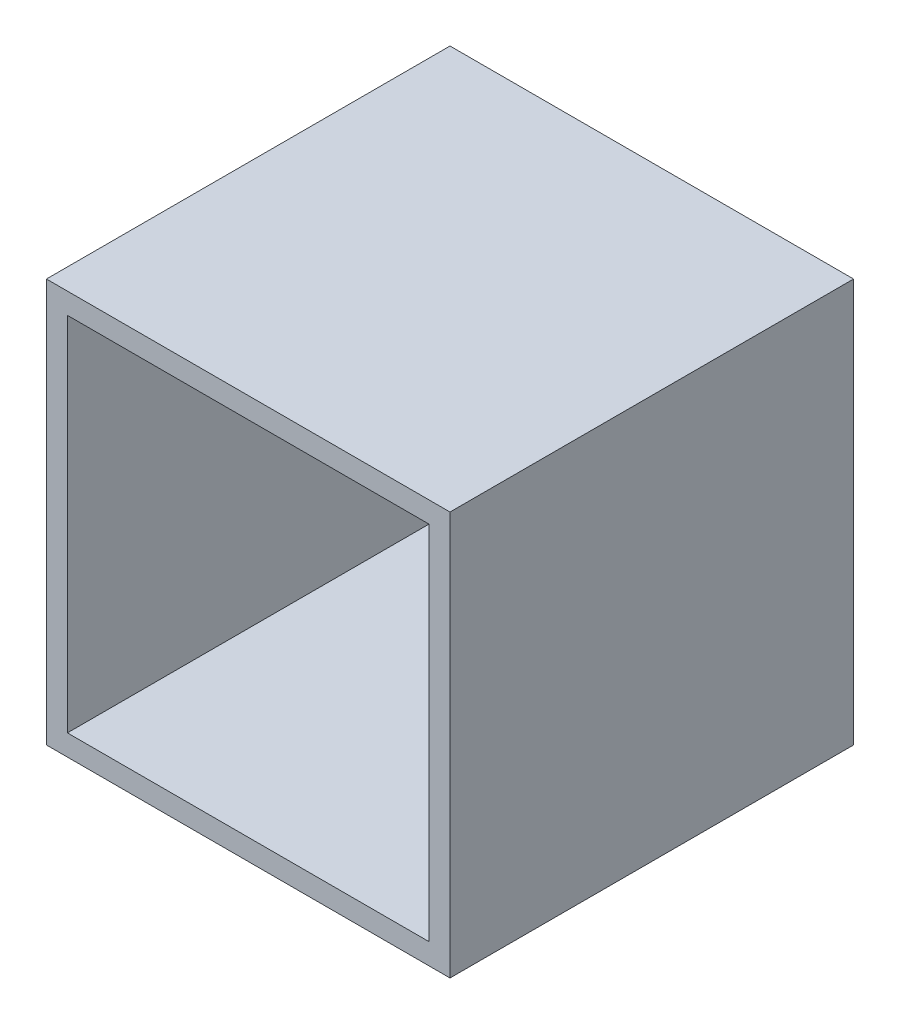
SolidWorks part; units mm, degrees
note: The reader was unsure of these and kept them because the rebuilt part matched: shared geometry of "Sketch1<2>".
ref_plane "Front Plane" through (0, 0, 0) normal (0, 0, 1) x (1, 0, 0)
ref_plane "Top Plane" through (0, 0, 0) normal (0, 1, 0) x (1, 0, 0)
ref_plane "Right Plane" through (0, 0, 0) normal (1, 0, 0) x (0, 0, -1)
sketch "Sketch1" plane through (0, 0, 0) normal (0, 0, 1) x (1, 0, 0)
  line L1 (-31.75, -31.75) -> (31.75, -31.75)
  line L2 (-31.75, -31.75) -> (-31.75, 31.75)
  line L3 (-31.75, 31.75) -> (31.75, 31.75)
  line L4 (31.75, -31.75) -> (31.75, 31.75)
  line L5 (-31.75, -31.75) -> (31.75, 31.75) construction
  line L6 (-31.75, 31.75) -> (31.75, -31.75) construction
  line L7 (-28.448, -28.448) -> (28.448, -28.448)
  line L8 (-28.448, -28.448) -> (-28.448, 28.448)
  line L9 (-28.448, 28.448) -> (28.448, 28.448)
  line L10 (28.448, -28.448) -> (28.448, 28.448)
  line L11 (-28.448, -28.448) -> (28.448, 28.448) construction
  line L12 (-28.448, 28.448) -> (28.448, -28.448) construction
  point P0 (0, 0)
  point P6 (0, 0)
  dimension "D1" = 63.5
  dimension "D2" = 63.5
  dimension "D3" = 3.302
  dimension "D4" = 3.302
surface "Surface-Plane1" sketch "Sketch1"
ref_plane "Plane1" through (-28.448, 28.448, 0) normal (0, 1, 0) x (1, 0, 0)
extrude "Boss-Extrude1" add sketch "Sketch1<2>" along normal blind 63.5
sketch "Sketch1<2>" plane through (0, 0, 0) normal (0, 0, 1) x (1, 0, 0) same geometry as "Sketch1"
sketch "Sketch2" plane through (0, 31.75, 0) normal (0, 1, 0) x (1, 0, 0)
  line L1 (-31.75, 0) -> (-12.7, 0)
  line L2 (-31.75, 0) -> (-31.75, -19.05)
  line L3 (-31.75, -19.05) -> (-12.7, -19.05)
  line L4 (-12.7, 0) -> (-12.7, -19.05)
  dimension "D1" = 19.05
  dimension "D2" = 19.05
